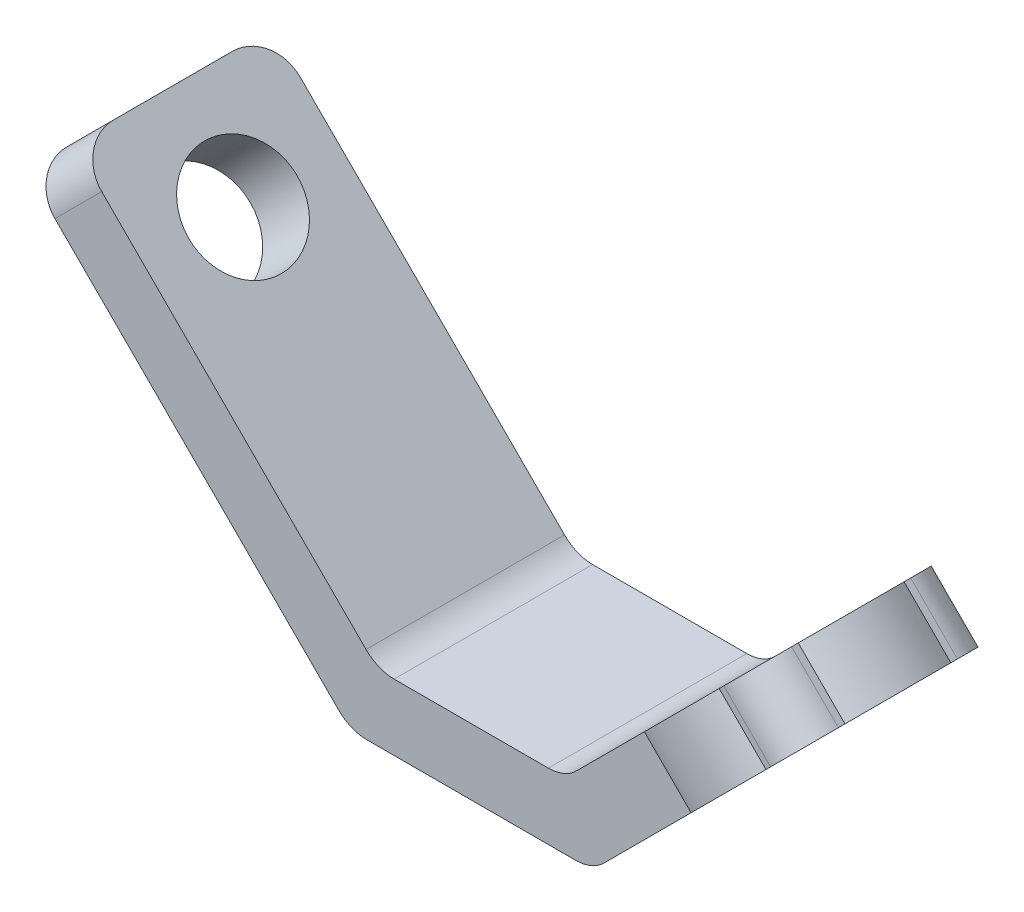
SolidWorks part; units mm, degrees
ref_plane "正面" through (0, 0, 0) normal (0, 0, 1) x (1, 0, 0)
ref_plane "平面" through (0, 0, 0) normal (0, 1, 0) x (1, 0, 0)
ref_plane "右側面" through (0, 0, 0) normal (1, 0, 0) x (0, 0, -1)
sketch "ｽｹｯﾁ1" plane through (0, 0, 0) normal (0, 0, 1) x (1, 0, 0)
  line L0 (0, 0) -> (-24.4454, 24.4454)
  line L1 (-24.4454, 24.4454) -> (-20.9099, 27.981)
  line L2 (-20.9099, 27.981) -> (2.0711, 5)
  line L3 (2.0711, 5) -> (16.2132, 5)
  line L4 (16.2132, 5) -> (30.3553, 19.1421)
  line L5 (30.3553, 19.1421) -> (33.8909, 15.6066)
  line L6 (33.8909, 15.6066) -> (18.2843, 0)
  line L7 (18.2843, 0) -> (0, 0)
  point P6 (23.2843, 12.0711)
  point P10 (-15.6066, 22.6777)
  dimension "D1" = 135
  dimension "D2" = 135
  dimension "D3" = 5
  dimension "D4" = 5
  dimension "D5" = 5
  dimension "D8" = 25
  dimension "D6" = 7.5
  dimension "D7" = 40
  dimension "D9" = 20
extrude "ﾎﾞｽ - 押し出し1" add sketch "ｽｹｯﾁ1" along normal mid plane 15
sketch "ｽｹｯﾁ2" plane through (0, 0, 0) normal (-0.7071, -0.7071, 0) x (0, 0, 1)
  line L1 (7.5, 34.5711) -> (-7.5, 34.5711) construction
  circle A0 centre (0, 27.0711) radius 4.1
  dimension "D1" = 8.2
  dimension "D2" = 7.5
extrude "ｶｯﾄ - 押し出し1" cut sketch "ｽｹｯﾁ2" against normal through all both and the other way through all
sketch "ｽｹｯﾁ6" plane through (9.1421, -9.1421, 0) normal (0.7071, -0.7071, 0) x (0, 0, -1)
  line L0 (-7.5, 35) -> (7.5, 35) construction
  circle A0 centre (0, 27.5) radius 8.5
  point P4 (0, 35)
  dimension "D2" = 17
  dimension "D1" = 7.5
extrude "ﾎﾞｽ - 押し出し2" add sketch "ｽｹｯﾁ6" against normal up to surface (5 mm away) up to face at (23.2843, 12.0711, 0)
sketch "ｽｹｯﾁ3" plane through (9.1421, -9.1421, 0) normal (0.7071, -0.7071, 0) x (0, 0, -1)
  line L1 (-7.5, 35) -> (-4, 35) construction
  circle A0 centre (0, 27.5) radius 4.1
  arc A3 (4, 35) -> (-4, 35) centre (0, 27.5) ccw construction
  point P2 (0, 0)
  point P3 (0, 0)
  point P10 (0, 27.5)
  point P11 (0, 36)
  dimension "D1" = 8.2
  dimension "D2" = 7.5
extrude "ｶｯﾄ - 押し出し2" cut sketch "ｽｹｯﾁ3" against normal blind 1 and the other way through all
fillet "ﾌｨﾚｯﾄ1" radius 3 8 edges at (32.1231, 17.3744, -7.5) (32.1231, 17.3744, 7.5) (-22.6777, 26.2132, -7.5) (-22.6777, 26.2132, 7.5) (18.2843, 0, 0) (0, 0, 0) (16.2132, 5, 0) (2.0711, 5, 0)
sketch "ｽｹｯﾁ4" plane through (9.1421, -9.1421, 0) normal (0.7071, -0.7071, 0) x (0, 0, -1)
  circle A0 centre (0, 27.5) radius 6 construction
  circle A1 centre (-6, 27.5) radius 1.4
  circle A2 centre (-3, 32.6962) radius 1.4
  circle A3 centre (3, 32.6962) radius 1.4
  circle A4 centre (6, 27.5) radius 1.4
  circle A5 centre (3, 22.3038) radius 1.4
  circle A6 centre (-3, 22.3038) radius 1.4
  point P5 (0, 27.5)
  point P18 (0, 27.5)
  dimension "D1" = 12
  dimension "D2" = 2.8
  dimension "D3" = 6
extrude "ｶｯﾄ - 押し出し3" cut sketch "ｽｹｯﾁ4" against normal blind 10
equation "\"D4@ｽｹｯﾁ1\"=\"D3@ｽｹｯﾁ1\""
equation "\"D5@ｽｹｯﾁ1\"=\"D3@ｽｹｯﾁ1\""
